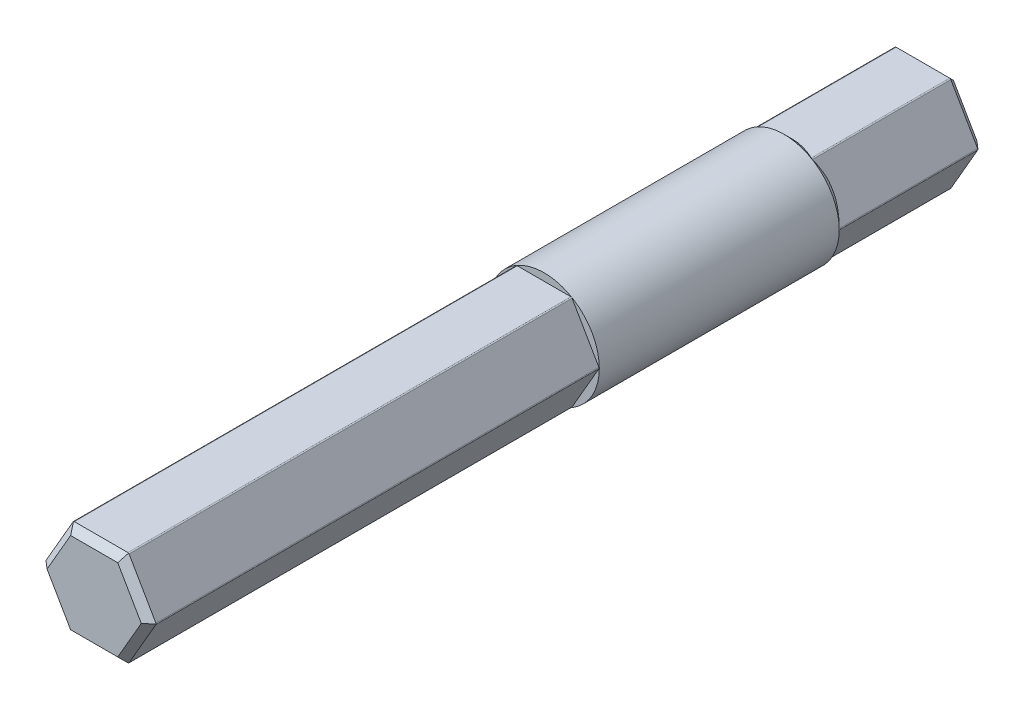
SolidWorks part; units mm, degrees
material "PETG"
ref_plane "Front Plane" through (0, 0, 0) normal (0, 0, 1) x (1, 0, 0)
ref_plane "Top Plane" through (0, 0, 0) normal (0, 1, 0) x (1, 0, 0)
ref_plane "Right Plane" through (0, 0, 0) normal (1, 0, 0) x (0, 0, -1)
sketch "Sketch1" plane through (0, 0, 0) normal (0, 0, 1) x (1, 0, 0)
  circle A0 centre (0, 0) radius 3.975
  dimension "Shaft Dia" = 7.95
extrude "Boss-Extrude1" add sketch "Sketch1" along normal blind 17.775
sketch "Sketch2" plane through (0, 0, 17.775) normal (0, 0, 1) x (1, 0, 0)
  line L1 (4, 0) -> (2, 3.4641) construction
  line L2 (2, 3.4641) -> (-2, 3.4641) construction
  line L3 (-2, 3.4641) -> (-4, 0) construction
  line L4 (-4, 0) -> (-2, -3.4641) construction
  line L5 (-2, -3.4641) -> (2, -3.4641) construction
  line L6 (2, -3.4641) -> (4, 0) construction
  line L7 (3.9711, 0) -> (1.9856, 3.4391)
  line L8 (1.9856, 3.4391) -> (-1.9856, 3.4391)
  line L9 (-1.9856, 3.4391) -> (-3.9711, 0)
  line L10 (-3.9711, 0) -> (-1.9856, -3.4391)
  line L11 (-1.9856, -3.4391) -> (1.9856, -3.4391)
  line L12 (1.9856, -3.4391) -> (3.9711, 0)
  circle A0 centre (0, 0) radius 3.4641 construction
  circle A1 centre (0, 0) radius 3.4391 construction
  dimension "Hex Circumscribed Nominal Dia" = 8
  dimension "Hex Flat To Flat Offset" = 0.025
extrude "Boss-Extrude2" add sketch "Sketch2" along normal blind 32.4
sketch "Sketch3" plane through (0, 0, 0) normal (0, 0, -1) x (-1, 0, 0)
  line L0 (-1.9856, 3.4391) -> (1.9856, 3.4391) construction
  line L13 (3.9711, 0) -> (1.9856, 3.4391)
  line L14 (1.9856, 3.4391) -> (-1.9856, 3.4391)
  line L15 (-1.9856, 3.4391) -> (-3.9711, 0)
  line L16 (-3.9711, 0) -> (-1.9856, -3.4391)
  line L17 (-1.9856, -3.4391) -> (1.9856, -3.4391)
  line L18 (1.9856, -3.4391) -> (3.9711, 0)
  circle A1 centre (0, 0) radius 3.4391 construction
extrude "Boss-Extrude3" add sketch "Sketch3" along normal blind 10
chamfer "Chamfer1" distance 0.5 angle 45 12 edges at (0, -3.4391, 50.175) (-2.9783, -1.7196, 50.175) (-2.9783, 1.7196, 50.175) (0, 3.4391, 50.175) (2.9783, 1.7196, 50.175) (2.9783, -1.7196, 50.175) (0, -3.4391, -10) (2.9783, -1.7196, -10) (2.9783, 1.7196, -10) (0, 3.4391, -10) (-2.9783, 1.7196, -10) (-2.9783, -1.7196, -10)
fillet "Fillet1" radius 0.1 12 edges at (-1.9856, 3.4391, -4.75) (-3.9711, 0, -4.75) (1.9856, 3.4391, -4.75) (3.9711, 0, -4.75) (1.9856, -3.4391, -4.75) (-1.9856, -3.4391, -4.75) (1.9856, -3.4391, 33.725) (-1.9856, -3.4391, 33.725) (-3.9711, 0, 33.725) (-1.9856, 3.4391, 33.725) (3.9711, 0, 33.725) (1.9856, 3.4391, 33.725)
chamfer "Chamfer2" distance 0.5 angle 45 1 edges at (3.975, 0, 0)
equation "\"tol_dia_id_intfc\" = 0.0500mm ' For hole diameters - Interference fit"
equation "\"tol_dia_id_slip\"  = 0.0750mm ' For hole diameters - Slip fit"
equation "\"tol_dia_id_clear\" = 0.1000mm ' For hole diameters - Clearance fit"
equation "\"tol_dia_od_intfc\" = 0.0500mm ' For shaft diameters - Interference fit"
equation "\"tol_dia_od_slip\"  = 0.0750mm ' For shaft diameters - Slip fit"
equation "\"tol_dia_od_clear\" = 0.1000mm ' For shaft diameters - Clearance fit"
equation "\"tol_general_intfc\"= 0.0250mm ' For general parts (Horiz) - Interference fit"
equation "\"tol_general_slip\" = 0.0375mm ' For general parts (Horiz) - Slip fit"
equation "\"tol_general_clear\"= 0.0500mm ' For general parts (Horiz) - Clearance fit"
equation "\"tol_layer_intfc\"  = 0.0250mm ' For all parts (Vert) - Interference fit"
equation "\"tol_layer_slip\"   = 0.0375mm ' For all parts (Vert) - Slip fit"
equation "\"tol_layer_clear\"  = 0.0500mm ' For all parts (Vert) - Clearance fit"
equation "\"tol_corner_rad\"   = 0.100mm ' For corners that fit into other parts"
equation "\"Shaft Dia@Sketch1\" = \"nominal_dia\" - \"tol_dia_od_intfc\""
equation "\"nominal_dia\"= 8.00mm"
equation "\"Hex Circumscribed Nominal Dia@Sketch2\" = \"nominal_dia\""
equation "\"Hex Flat To Flat Offset@Sketch2\" = \"tol_general_intfc\""
equation "\"D1@Fillet1\"=\"tol_corner_rad\""
equation "\"D1@Boss-Extrude2\"=32.50mm-\"tol_layer_clear\"*2"
